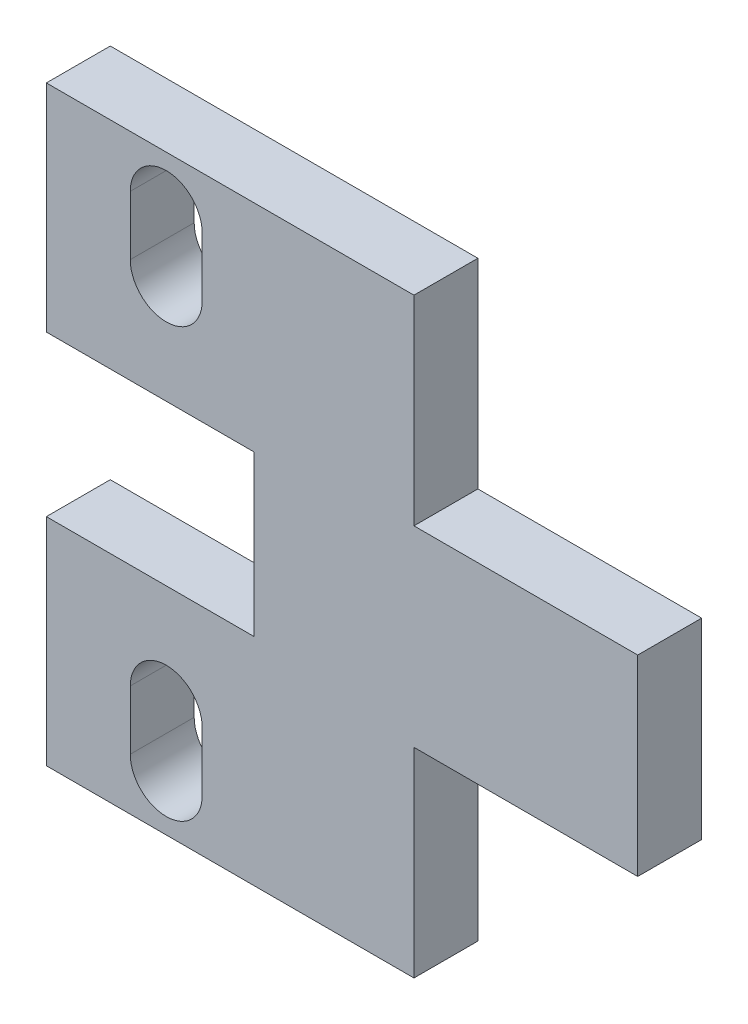
SolidWorks part; units mm, degrees
ref_plane "Front Plane" through (0, 0, 0) normal (0, 0, 1) x (1, 0, 0)
ref_plane "Top Plane" through (0, 0, 0) normal (0, 1, 0) x (1, 0, 0)
ref_plane "Right Plane" through (0, 0, 0) normal (1, 0, 0) x (0, 0, -1)
sketch "Sketch1" plane through (0, 0, 0) normal (0, 0, 1) x (1, 0, 0)
  line L0 (0, 0) -> (0, -5)
  line L1 (0, -5) -> (-13, -5)
  line L2 (-13, -5) -> (-13, -18.5)
  line L3 (-13, -18.5) -> (10, -18.5)
  line L4 (10, -18.5) -> (10, -6)
  line L5 (10, -6) -> (24, -6)
  line L6 (24, -6) -> (24, 0)
  line L7 (0, 0) -> (24, 0)
  dimension "D1" = 13.5
  dimension "D2" = 12.5
  dimension "D3" = 23
  dimension "D4" = 5
  dimension "D5" = 6
  dimension "D6" = 37
  dimension "D7" = 13
extrude "Boss-Extrude1" add sketch "Sketch1" along normal mid plane 4
hole_wizard "M4 Clearance Slot1" positions "Sketch5" profile "Sketch6" size "M4" standard "ANSI Metric" slot yes end condition through all
sketch "Sketch5" plane through (0, 0, 2) normal (0, 0, 1) x (1, 0, 0)
  line L0 (-5.5, -9.3) -> (-5.5, -17.5) construction
  line L1 (-13, -5) -> (-13, -18.5) construction
  line L2 (-13, -18.5) -> (10, -18.5) construction
  point P0 (-5.5, -13.4)
  point P5 (0, 0)
  point P8 (-7.3949, -12.5116)
  point P9 (0, 0)
  dimension "D1" = 8.2
  dimension "D2" = 1
  dimension "D3" = 7.5
sketch "Sketch6" plane through (-5.5, -13.4, 2) normal (1, 0, 0) x (0, -1, 0)
  line L0 (0, 0) -> (0, 4)
  line L1 (0, 4) -> (2.25, 4)
  line L2 (2.25, 4) -> (2.25, 0)
  line L5 (2.25, 0) -> (0, 0)
  line L11 (0, -6.35) -> (0, 107.95) construction
  dimension "Thru Hole Dia." = 4.5
  dimension "Thru Hole Depth" = 4
mirror "Mirror2" about plane through (0, 0, 0) normal (0, 1, 0) of "M4 Clearance Slot1", "Boss-Extrude1"
